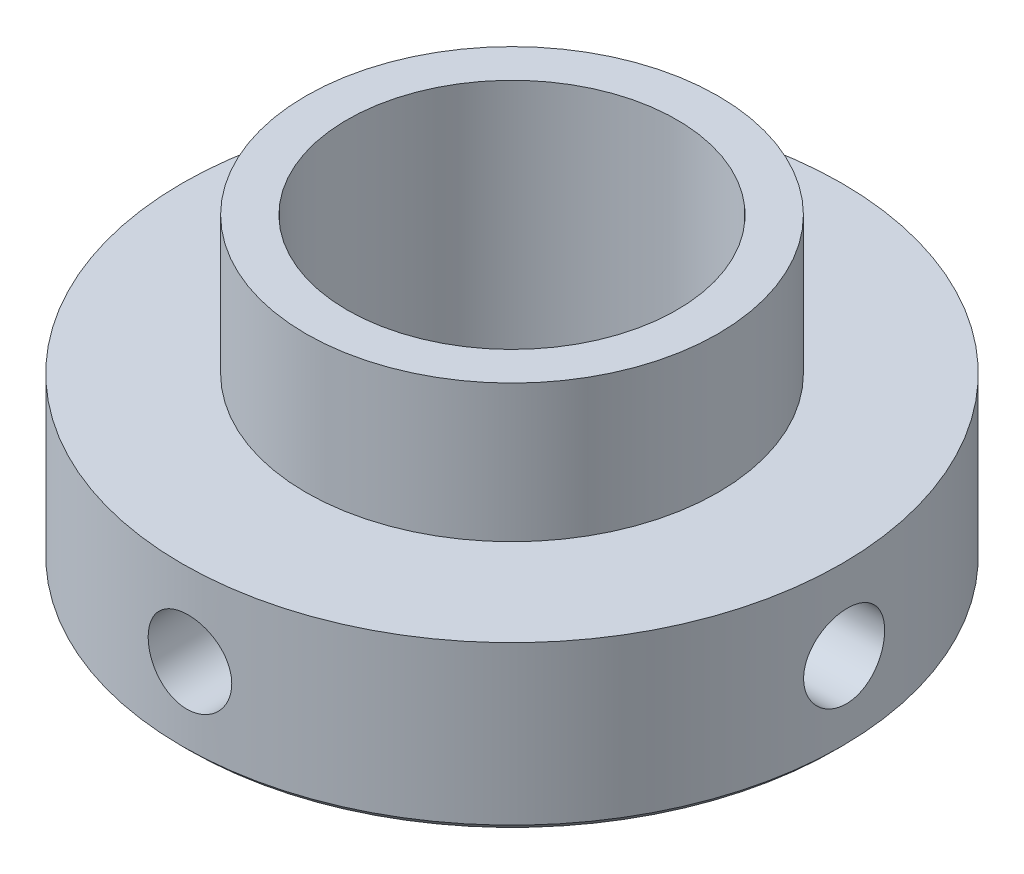
SolidWorks part; units mm, degrees
ref_plane "Front Plane" through (0, 0, 0) normal (0, 0, 1) x (1, 0, 0)
ref_plane "Top Plane" through (0, 0, 0) normal (0, 1, 0) x (1, 0, 0)
ref_plane "Right Plane" through (0, 0, 0) normal (1, 0, 0) x (0, 0, -1)
sketch "Sketch1" plane through (0, 0, 0) normal (0, 1, 0) x (1, 0, 0)
  circle A0 centre (0, 0) radius 3
  circle A1 centre (0, 0) radius 1.5
  circle A2 centre (0, 0) radius 1.875
  dimension "D1" = 6
  dimension "D2" = 3
  dimension "D3" = 3.75
extrude "Boss-Extrude1" add sketch "Sketch1" along normal mid plane 1.5 contours A0
extrude "Boss-Extrude2" add sketch "Sketch1<3>" along normal blind 1.25 from offset 0.75 contours A2
sketch "Sketch1<3>" plane through (0, 0, 0) normal (0, 1, 0) x (1, 0, 0) same geometry as "Sketch1"
extrude "Cut-Extrude1" cut sketch "Sketch1<4>" against normal through all both and the other way through all contours A1
sketch "Sketch1<4>" plane through (0, 0, 0) normal (0, 1, 0) x (1, 0, 0) same geometry as "Sketch1"
hole_wizard "Ø1.0mm Dowel Hole1" positions "3DSketch2" profile "Sketch4" hole size "Ø1.0" standard "ISO"
sketch3d "3DSketch2"
  point P0 (0, 0, 0)
  point P3 (0, 0, 0)
  point P5 (0.0463, 0, 2.9996)
  dimension "D1" = 0.75
sketch "Sketch4" plane through (0.0463, 0, 2.9996) normal (0, 1, 0) x (0.9999, 0, -0.0154)
  line L0 (0, 0) -> (0, 1.525)
  line L1 (0, 1.525) -> (0.3745, 1.3)
  line L2 (0.3745, 1.3) -> (0.3745, 0)
  line L5 (0.3745, 0) -> (0, 0)
  line L10 (0, 1.525) -> (-0.3745, 1.3) construction
  line L11 (0, -6.35) -> (0, 107.95) construction
  dimension "Hole Dia." = 0.749
  dimension "Hole Depth" = 1.3
  dimension "Drill Angle" = 118
pattern_circular "CirPattern1" count 4 over 360 about axis through (0, 0.75, 0) along (0, 1, 0) of "Ø1.0mm Dowel Hole1"
chamfer "Chamfer1" distance 0.062 angle 45 1 edges at (0, -0.75, 3)
